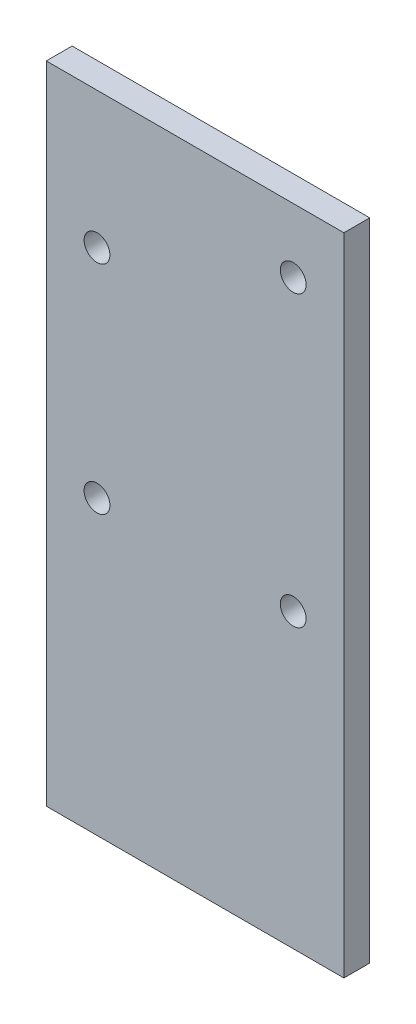
SolidWorks part; units mm, degrees
ref_plane "정면" through (0, 0, 0) normal (0, 0, 1) x (1, 0, 0)
ref_plane "윗면" through (0, 0, 0) normal (0, 1, 0) x (1, 0, 0)
ref_plane "우측면" through (0, 0, 0) normal (1, 0, 0) x (0, 0, -1)
sketch "스케치1" plane through (0, 0, 0) normal (0, 0, 1) x (1, 0, 0)
  line L1 (-28.82, 62.5) -> (28.82, 62.5)
  line L2 (-28.82, 62.5) -> (-28.82, -62.5)
  line L3 (-28.82, -62.5) -> (28.82, -62.5)
  line L4 (28.82, 62.5) -> (28.82, -62.5)
  line L5 (-28.82, 62.5) -> (28.82, -62.5) construction
  line L6 (-28.82, -62.5) -> (28.82, 62.5) construction
  point P0 (0, 0)
  dimension "D1" = 57.64
  dimension "D2" = 125
extrude "보스-돌출1" add sketch "스케치1" along normal blind 5
sketch "스케치2" plane through (0, 0, 5) normal (0, 0, 1) x (1, 0, 0)
  line L0 (28.82, 62.5) -> (-28.82, 62.5) construction
  line L1 (28.82, -62.5) -> (28.82, 62.5) construction
  circle A10 centre (-19, 36.1) radius 5.8
  circle A11 centre (-19, 36.1) radius 2.5
  circle A12 centre (19, 50.1) radius 5.8
  circle A13 centre (19, 50.1) radius 2.5
  circle A14 centre (-19, -5.9) radius 5.8
  circle A15 centre (-19, -5.9) radius 2.5
  circle A16 centre (19, -5.9) radius 5.8
  circle A17 centre (19, -5.9) radius 2.5
  point P17 (0, 0)
  point P18 (-19, -5.9)
  dimension "D3" = 5
  dimension "D4" = 11.6
  dimension "D5" = 5
  dimension "D8" = 11.6
  dimension "D9" = 11.6
  dimension "D10" = 42
  dimension "D11" = 56
  dimension "D12" = 38
  dimension "D13" = 9.82
  dimension "D2" = 11.6
  dimension "D6" = 5
  dimension "D7" = 5
  dimension "D14" = 12.4
  dimension "D15" = 38
  dimension "D16" = 68.4
  dimension "D17" = 38
extrude "컷-돌출1" cut sketch "스케치2" against normal blind 5 contours A13 | A17 | A15 | A11 region at (19, 50.1, 5) region at (-19, -5.9, 5) region at (19, -5.9, 5)
